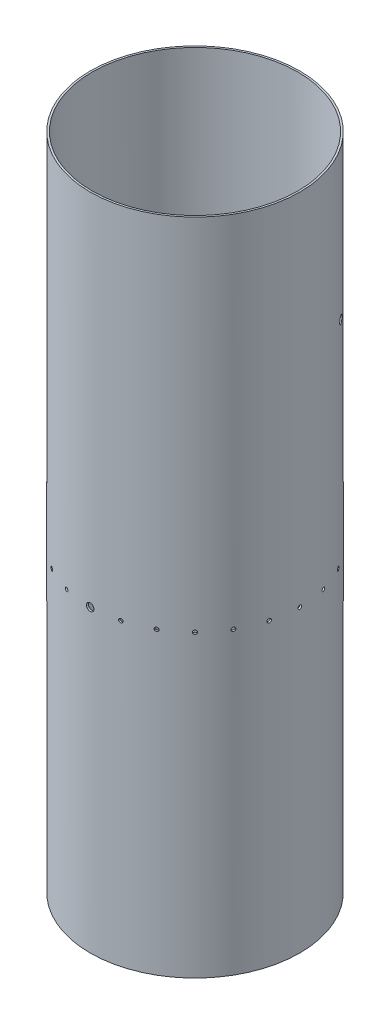
SolidWorks part; units mm, degrees
ref_plane "Front Plane" through (0, 0, 0) normal (0, 0, 1) x (1, 0, 0)
ref_plane "Top Plane" through (0, 0, 0) normal (0, 1, 0) x (1, 0, 0)
ref_plane "Right Plane" through (0, 0, 0) normal (1, 0, 0) x (0, 0, -1)
sketch "Sketch1" plane through (0, 0, 0) normal (0, 1, 0) x (1, 0, 0)
  circle A0 centre (0, 0) radius 88.9
  circle A1 centre (0, 0) radius 87.3125
  dimension "D1" = 177.8
  dimension "D2" = 174.625
extrude "Boss-Extrude1" add sketch "Sketch1" along normal blind 558.8
ref_plane "Plane1" through (0, 0, 88.9) normal (0, 0, 1) x (1, 0, 0)
sketch "Sketch10" plane through (0, 0, 88.9) normal (0, 0, 1) x (1, 0, 0)
  line L0 (88.9, 558.8) -> (-88.9, 558.8) construction
  circle A0 centre (0, 254) radius 1.5875
  dimension "D1" = 3.175
  dimension "D2" = 304.8
extrude "Cut-Extrude1" cut sketch "Sketch10" against normal blind 3.81
ref_axis "Axis1" through (0, 558.8, 0) along (0, -1, 0)
pattern_circular "CirPattern1" count 24 over 360 about axis through (0, 558.8, 0) along (0, -1, 0) of "Cut-Extrude1"
sketch "Sketch12" plane through (0, 0, 88.9) normal (0, 0, 1) x (1, 0, 0)
  circle A0 centre (0, 254) radius 3.175
  dimension "D1" = 6.35
extrude "Cut-Extrude2" cut sketch "Sketch12" against normal through all both and the other way through all
ref_axis "Axis2" through (0, 254, 87.0756) along (0, 0, 1)
sketch "Sketch15" plane through (0, 0, 0) normal (1, 0, 0) x (0, 0, -1)
  line L1 (0, 558.8) -> (0, 0) construction
  circle A2 centre (50.8, 431.8) radius 3.175
  circle A3 centre (0, 254) radius 1.5875 construction
  dimension "D1" = 6.35
  dimension "D3" = 50.8
  dimension "D2" = 177.8
extrude "Cut-Extrude4" cut sketch "Sketch15" against normal through all both and the other way through all
